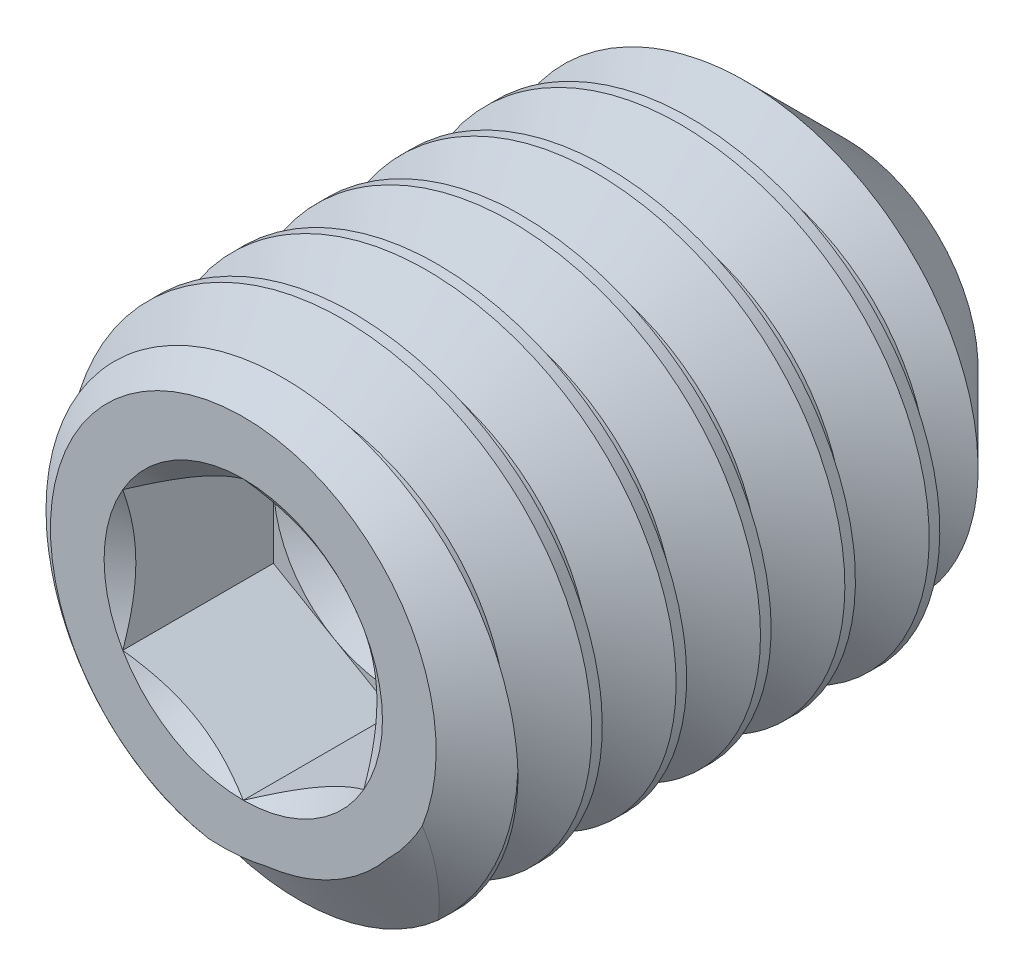
SolidWorks part; units mm, degrees
ref_plane "Front" through (0, 0, 0) normal (0, 0, 1) x (1, 0, 0)
ref_plane "Top" through (0, 0, 0) normal (0, 1, 0) x (1, 0, 0)
ref_plane "Right" through (0, 0, 0) normal (1, 0, 0) x (0, 0, -1)
sketch "Body Sketch" plane through (0, 0, 0) normal (1, 0, 0) x (0, 0, -1)
  line L0 (-2.1707, 0) -> (-2.1707, 1.6)
  line L1 (-2.1707, 1.6) -> (-1.8907, 2)
  line L2 (-1.8907, 2) -> (1.9252, 2)
  line L3 (1.9252, 2) -> (2.8293, 1.0959)
  line L4 (0.0173, 2) -> (0.0173, -2) construction
  line L5 (2.1707, 0) -> (-2.1707, 0)
  line L6 (-2.1707, 1.6) -> (-2.1707, -1.6) construction
  line L7 (2.1707, 0) -> (2.8293, 1.0959)
  line L8 (2.1707, 0) -> (2.8293, -1.0959) construction
  line L10 (2.1707, 0) -> (2.8293, 0) construction
  line L11 (2.8293, 1.0959) -> (2.8293, 0) construction
  point P11 (0.0173, 0)
  dimension "Length" = 5
  dimension "Top Chamfer" = 35
  dimension "Diameter" = 4
  dimension "D1" = 3.2
  dimension "D2" = 118
  dimension "D3" = 45
revolve "Body Revolve" add sketch "Body Sketch" angle 360 about L5
ref_plane "Bottom of Tip Plane" through (0, 0, -2.8293) normal (0, 0, 1) x (1, 0, 0)
sketch "Spiral Sketch" plane through (0, 0, -2.8293) normal (0, 0, 1) x (1, 0, 0)
  circle A0 centre (0, 0) radius 2 construction
  circle A1 centre (0, 0) radius 2
curve "Helix/Spiral" pitch 0.7 height 5.7 radius 2 centre (0, 0, -2.8293) axis (0, 0, 1) start towards (0, 1, 0) parameters "Thread Pitch"=0.7
sketch "Cut Sweep Sketch" plane through (0, 0, 0) normal (1, 0, 0) x (0, 0, -1)
  line L0 (2.8293, 2) -> (3.4418, 2)
  line L1 (3.4418, 2) -> (3.1793, 1.5453)
  line L2 (3.1793, 1.5453) -> (3.0918, 1.5453)
  line L3 (3.0918, 1.5453) -> (2.8293, 2)
  line L4 (2.9605, 1.7727) -> (3.3105, 1.7727) construction
  line L6 (-1.8907, 2) -> (1.9252, 2) construction
  dimension "D1" = 0.0875
  dimension "D3" = 60
  dimension "D2" = 0.35
sweep "Cut Sweep" cut profiles "Cut Sweep Sketch" path "Helix/Spiral" align with end faces yes
sketch "Hex Sketch" plane through (0, 0, 2.1707) normal (0, 0, 1) x (1, 0, 0)
  line L1 (0, 1.1547) -> (-1, 0.5774)
  line L2 (-1, 0.5774) -> (-1, -0.5774)
  line L3 (-1, -0.5774) -> (0, -1.1547)
  line L4 (0, -1.1547) -> (1, -0.5774)
  line L5 (1, -0.5774) -> (1, 0.5774)
  line L6 (1, 0.5774) -> (0, 1.1547)
  circle A0 centre (0, 0) radius 1 construction
  dimension "Hex" = 2
extrude "Hex Extrude" cut sketch "Hex Sketch" against normal blind 1.25
sketch "Hex Entry Sketch" plane through (0, 0, 2.1707) normal (0, 0, 1) x (1, 0, 0)
  circle A0 centre (0, 0) radius 1.1547
extrude "Hex Entry Extrude" cut sketch "Hex Entry Sketch" against normal through all draft 55
sketch "Hex Bottom Sketch" plane through (0, 0, 0.9207) normal (0, 0, 1) x (1, 0, 0)
  circle A0 centre (0, 0) radius 1 construction
  circle A1 centre (0, 0) radius 1
extrude "Hex Bottom Extrude" cut sketch "Hex Bottom Sketch" against normal through all draft 60
equation "\"D1@Cut Sweep Sketch\" = \"Thread Pitch@Helix/Spiral\" * .125"
equation "\"D2@Cut Sweep Sketch\" = \"Thread Pitch@Helix/Spiral\" * .5"
equation "\"D3@Helix/Spiral\" = \"Length@Body Sketch\" + \"Thread Pitch@Helix/Spiral\""
equation "\"hex Depth@Hex Extrude\" = \"Hex@Hex Sketch\" * .625"
equation "\"D1@Body Sketch\" = \"Diameter@Body Sketch\" * .8"
equation "\"Diameter\"= 4mm"
equation "\"Thread Pitch\"= 0.7mm"
equation "\"Hex Size\"= 2.0mm"
equation "\"Diameter@Body Sketch\"=\"Diameter\""
equation "\"Thread Pitch@Helix/Spiral\"=\"Thread Pitch\""
equation "\"Hex@Hex Sketch\"=\"Hex Size\""
